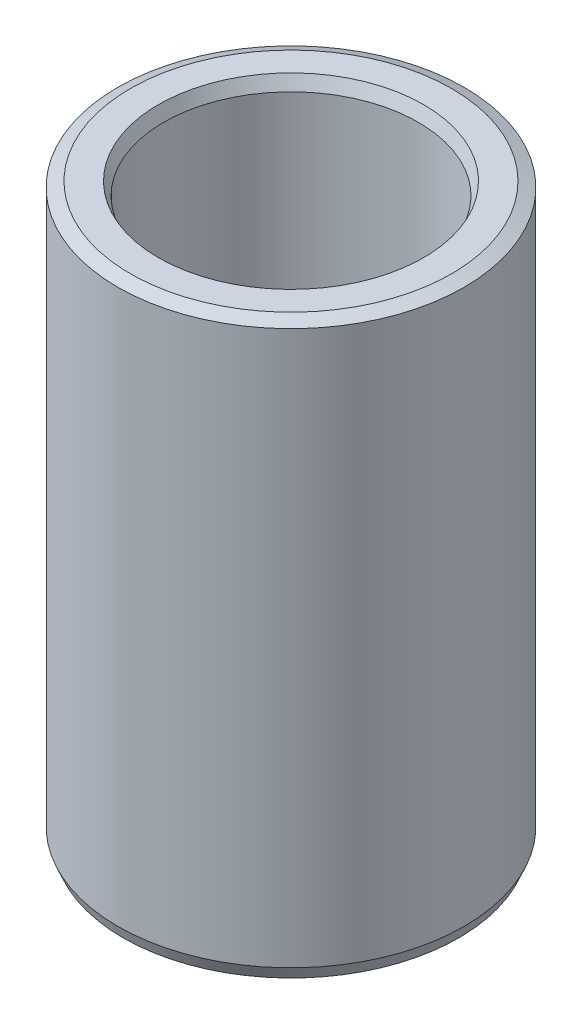
SolidWorks part; units mm, degrees
ref_plane "Front Plane" through (0, 0, 0) normal (0, 0, 1) x (1, 0, 0)
ref_plane "Top Plane" through (0, 0, 0) normal (0, 1, 0) x (1, 0, 0)
ref_plane "Right Plane" through (0, 0, 0) normal (1, 0, 0) x (0, 0, -1)
sketch "Sketch1" plane through (0, 0, 0) normal (0, 1, 0) x (1, 0, 0)
  circle A0 centre (0, 0) radius 55
  dimension "SLEEVE_OD" = 110
extrude "Boss-Extrude1" add sketch "Sketch1" along normal blind 181.4908
sketch "Sketch2" plane through (0, 0, 0) normal (0, 1, 0) x (1, 0, 0)
  circle A0 centre (0, 0) radius 40.4253
  dimension "BORE_D" = 80.8507
extrude "Cut-Extrude1" cut sketch "Sketch2" along normal through all
chamfer "Chamfer1" distance 1.6892 angle 67.185 4 edges at (0, 181.4908, 40.4253) (0, 0, 40.4253) (0, 0, 55) (0, 181.4908, 55) first distance on face at (0, 181.4908, 40.4253) first distance on face at (0, 0, 40.4253) first distance on face at (0, 181.4908, 55)
